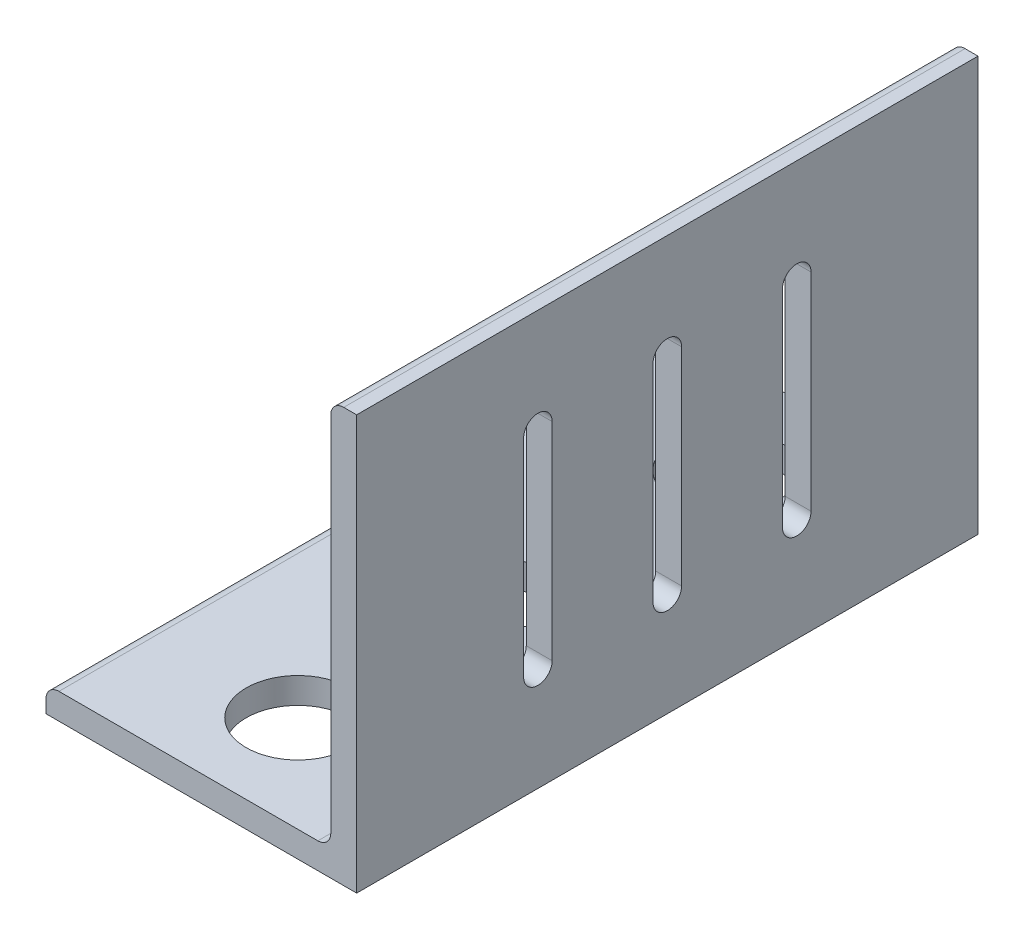
SolidWorks part; units mm, degrees
ref_plane "Front Plane" through (0, 0, 0) normal (0, 0, 1) x (1, 0, 0)
ref_plane "Top Plane" through (0, 0, 0) normal (0, 1, 0) x (1, 0, 0)
ref_plane "Right Plane" through (0, 0, 0) normal (1, 0, 0) x (0, 0, -1)
sketch "Sketch2" plane through (0, 0, 0) normal (0, 0, 1) x (1, 0, 0)
  line L0 (-38.1, 0) -> (38.1, 0)
  line L1 (38.1, 0) -> (38.1, 101.6)
  line L2 (38.1, 101.6) -> (31.75, 101.6) construction
  line L3 (31.75, 98.425) -> (31.75, 9.525)
  line L4 (28.575, 6.35) -> (-34.925, 6.35)
  line L5 (-38.1, 0) -> (-38.1, 6.35) construction
  line L6 (34.925, 101.6) -> (38.1, 101.6)
  line L7 (-38.1, 3.175) -> (-38.1, 0)
  arc A0 (31.75, 98.425) -> (34.925, 101.6) centre (34.925, 98.425) cw
  arc A1 (-38.1, 3.175) -> (-34.925, 6.35) centre (-34.925, 3.175) cw
  arc A2 (31.75, 9.525) -> (28.575, 6.35) centre (28.575, 9.525) cw
  dimension "Vert" = 101.6
  dimension "Horz" = 76.2
  dimension "Thickness" = 6.35
extrude "Boss-Extrude1" add sketch "Sketch2" along normal mid plane 152.4
ref_plane "Contact Plane 1" through (0, 6.35, 0) normal (0, 1, 0) x (1, 0, 0)
ref_plane "Contact Plane 2" through (31.75, 0, 0) normal (-1, 0, 0) x (0, 0, 1)
sketch "Sketch3" plane through (38.1, 0, 0) normal (1, 0, 0) x (0, 0, -1)
  line L0 (-31.75, 76.2) -> (-31.75, 25.4) construction
  line L1 (-28.25, 76.2) -> (-28.25, 25.4)
  line L2 (-35.25, 76.2) -> (-35.25, 25.4)
  line L3 (0, 0) -> (0, 101.6) construction
  line L4 (-76.2, 0) -> (76.2, 0) construction
  line L5 (-76.2, 101.6) -> (76.2, 101.6) construction
  line L6 (31.75, 76.2) -> (31.75, 25.4) construction
  line L7 (28.25, 76.2) -> (28.25, 25.4)
  line L8 (35.25, 76.2) -> (35.25, 25.4)
  line L9 (0, 76.2) -> (0, 25.4) construction
  line L10 (3.5, 76.2) -> (3.5, 25.4)
  line L11 (-3.5, 76.2) -> (-3.5, 25.4)
  arc A0 (-28.25, 76.2) -> (-35.25, 76.2) centre (-31.75, 76.2) ccw
  arc A1 (-35.25, 25.4) -> (-28.25, 25.4) centre (-31.75, 25.4) ccw
  arc A2 (28.25, 76.2) -> (35.25, 76.2) centre (31.75, 76.2) cw
  arc A3 (35.25, 25.4) -> (28.25, 25.4) centre (31.75, 25.4) cw
  arc A4 (3.5, 76.2) -> (-3.5, 76.2) centre (0, 76.2) ccw
  arc A5 (-3.5, 25.4) -> (3.5, 25.4) centre (0, 25.4) ccw
  point P2 (-31.75, 50.8)
  point P15 (31.75, 50.8)
  point P22 (0, 50.8)
  point P27 (0, 0)
  dimension "D1" = 3.5
  dimension "D3" = 31.75
  dimension "D5" = 3.5
  dimension "D2" = 50.8
  dimension "D4" = 50.8
  dimension "D6" = 50.8
  dimension "D7" = 50.8
extrude "Cut-Extrude1" cut sketch "Sketch3" against normal blind 10
sketch "Sketch4" plane through (0, 0, 0) normal (0, -1, 0) x (1, 0, 0)
  circle A2 centre (0, 0) radius 10
  circle A3 centre (0, 52.5) radius 12.7
  circle A4 centre (0, -52.5) radius 12.7
  point P11 (0, -33.6876)
  dimension "D3" = 20
  dimension "D6" = 25.4
  dimension "D7" = 52.5
  dimension "D8" = 52.5
extrude "Cut-Extrude2" cut sketch "Sketch4" against normal blind 10
